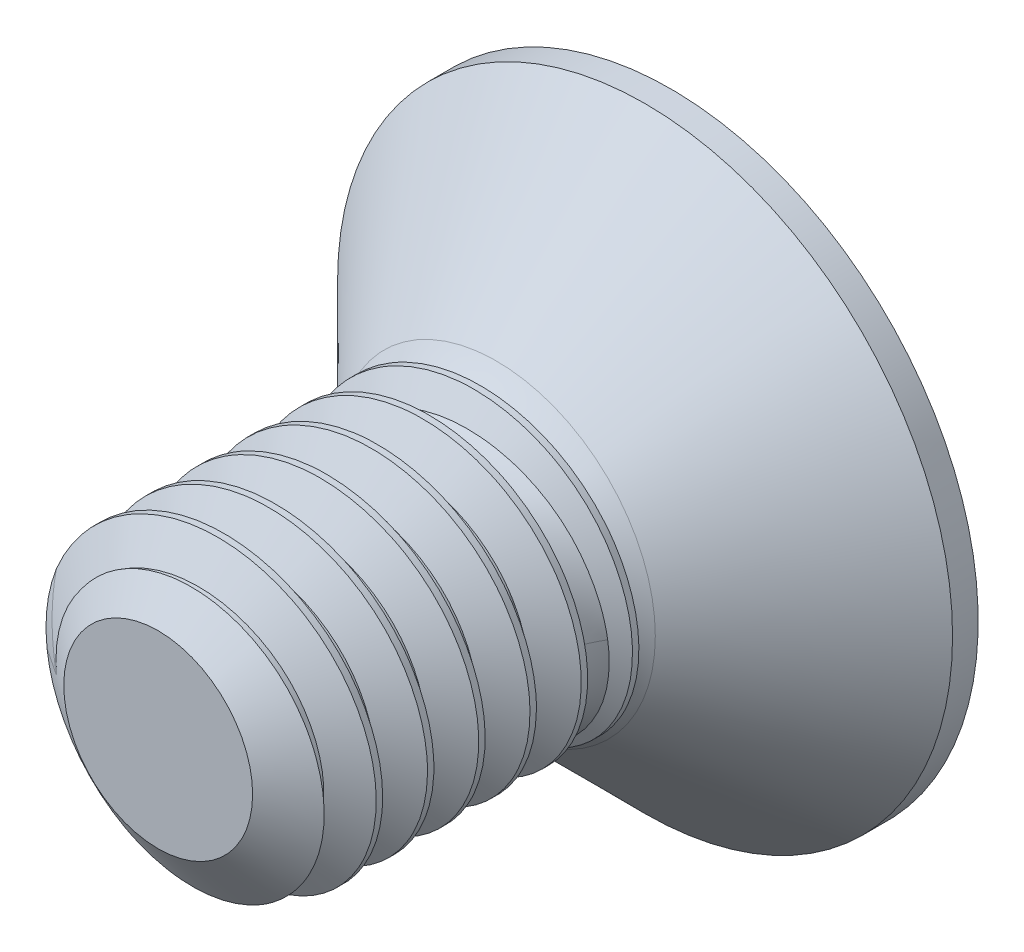
SolidWorks part; units mm, degrees
ref_plane "Front Plane" through (0, 0, 0) normal (0, 0, 1) x (1, 0, 0)
ref_plane "Top Plane" through (0, 0, 0) normal (0, 1, 0) x (1, 0, 0)
ref_plane "Right Plane" through (0, 0, 0) normal (1, 0, 0) x (0, 0, -1)
sketch "Sketch1" plane through (0, 0, 0) normal (0, 0, 1) x (1, 0, 0)
  circle A0 centre (0, 0) radius 1.5
  dimension "OD" = 3
extrude "Extrude1" add sketch "Sketch1" against normal blind 5
sketch "Sketch2" plane through (0, 0, 0) normal (0, 0, 1) x (1, 0, 0)
  circle A0 centre (0, 0) radius 1.5 construction
  circle A1 centre (0, 0) radius 1.5
curve "Helix/Spiral1" pitch 0.5 height 5.5 radius 1.5 centre (0, 0, 0) axis (0, 0, -1) start towards (0, 1, 0) parameters "pitch"=0.5
sketch "Sketch3" plane through (0, 0, 0) normal (1, 0, 0) x (0, 0, -1)
  line L0 (-0.4375, 1.5) -> (-0.25, 1.1752)
  line L1 (-0.25, 1.1752) -> (-0.1875, 1.1752)
  line L2 (-0.1875, 1.1752) -> (0, 1.5)
  line L3 (-0.4375, 1.5) -> (0, 1.5)
  line L4 (-0.2188, 1.5) -> (-0.2188, 1.1752) construction
  line L5 (-0.3438, 1.3376) -> (-0.0937, 1.3376) construction
  line L6 (0, 1.5) -> (0, -1.5) construction
  dimension "D1" = 0.0625
  dimension "D2" = 0.25
  dimension "D3" = 60
sweep "Cut-Sweep1" cut profiles "Sketch3" path "Helix/Spiral1"
sketch "Sketch4" plane through (0, 0, 0) normal (1, 0, 0) x (0, 0, -1)
  line L0 (0.4053, 1.5) -> (0, 0.9212)
  line L1 (0, 0.9212) -> (0, 1.5)
  line L2 (0.4053, 1.5) -> (0, 1.5)
  line L3 (-0.4375, 1.5) -> (0, 1.5) construction
  line L4 (0, 0) -> (7.0209, 0) construction
  dimension "D1" = 55
  dimension "D2" = 0.254
revolve "Cut-Revolve1" cut sketch "Sketch4" angle 360 about L4
sketch "Sketch5" plane through (0, 0, 0) normal (1, 0, 0) x (0, 0, -1)
  line L0 (5, -1.1822) -> (5, 1.0703) construction
  line L1 (5, 1.55) -> (18.1906, 1.55)
  line L2 (5, 1.55) -> (5, 0)
  line L3 (5, 0) -> (18, 0)
  line L4 (18, 1.2198) -> (18, 0)
  line L5 (18.1906, 1.55) -> (18, 1.2198)
  line L6 (0, 0) -> (9.9695, 0) construction
  point P3 (18, 1.55)
  point P10 (18, 1.55)
  dimension "D1" = 0.3302
  dimension "Thread min" = 18
  dimension "D2" = 0.05
  dimension "D3" = 30
revolve "partially thread" [suppressed] add sketch "Sketch5" angle 360 about L6
sketch "Sketch6" plane through (0, 0, -5) normal (0, 0, -1) x (-1, 0, 0)
  circle A0 centre (0, 0) radius 3
  dimension "head dia" = 6
extrude "Extrude2" add sketch "Sketch6" against normal blind 1.7
sketch "Sketch10" plane through (0, 0, 0) normal (1, 0, 0) x (0, 0, -1)
  line L0 (4.75, -3) -> (3.3, -1.55)
  line L1 (3.3, -1.55) -> (3.3, -3)
  line L2 (4.75, -3) -> (3.3, -3)
  line L3 (0, 0) -> (3.3, 0) construction
  line L4 (3.3, 3) -> (3.3, -3) construction
  line L5 (4.75, 3) -> (3.3, 3) construction
  line L6 (3.3, 1.55) -> (3.3, 3) construction
  line L7 (4.75, 3) -> (3.3, 1.55) construction
  line L8 (3.3, 3) -> (3.3, -3) construction
  line L9 (3.3, 1.55) -> (3.3, -1.55) construction
  dimension "D1" = 45
  dimension "D2" = 0.05
revolve "Cut-Revolve2" cut sketch "Sketch10" angle 360 about L3
sketch "Sketch11" plane through (0, 0, 0) normal (1, 0, 0) x (0, 0, -1)
  line L0 (-0.25, 1.1752) -> (-0.1875, 1.1752) construction
  line L1 (4.75, 3) -> (3.3, 1.55) construction
  line L2 (2.3953, 1.1752) -> (2.3953, 0)
  line L3 (2.3953, 0) -> (3.3, 0)
  line L4 (3.3, 1.55) -> (3.3, 0)
  line L5 (0, 0) -> (3.3, 0) construction
  arc A0 (3.3, 1.55) -> (2.3953, 1.1752) centre (2.3953, 2.4547) cw
revolve "Revolve1" add sketch "Sketch11" angle 360 about L3
sketch "Sketch7" plane through (0, 0, -5) normal (0, 0, 1) x (1, 0, 0)
  line L1 (0, 1.1547) -> (-1, 0.5774)
  line L2 (-1, 0.5774) -> (-1, -0.5774)
  line L3 (-1, -0.5774) -> (0, -1.1547)
  line L4 (0, -1.1547) -> (1, -0.5774)
  line L5 (1, -0.5774) -> (1, 0.5774)
  line L6 (1, 0.5774) -> (0, 1.1547)
  circle A0 centre (0, 0) radius 1 construction
  dimension "hex dia" = 2
extrude "Cut-Extrude1" cut sketch "Sketch7" along normal blind 1.5
sketch "Sketch8" plane through (0, 0, -5) normal (0, 0, 1) x (1, 0, 0)
  circle A0 centre (0, 0) radius 1.1547
extrude "Cut-Extrude2" cut sketch "Sketch8" along normal through all draft 45
sketch "Sketch9" plane through (0, 0, 0) normal (1, 0, 0) x (0, 0, -1)
  line L0 (0, 1.5) -> (0, -1.5) construction
  line L1 (2.75, 1.5) -> (2.75, -1.5) construction
  line L2 (3.3, 1.5) -> (3.3, -1.5) construction
  line L3 (3.3, -1.55) -> (3.3, -3) construction
  dimension "D1" = 2.75
equation "\"D3@Helix/Spiral1\" = \"screw length@Extrude1\"+\"pitch@Helix/Spiral1\""
equation "\"D1@Sketch3\" = \"pitch@Helix/Spiral1\"*.125"
equation "\"D2@Sketch3\" = \"pitch@Helix/Spiral1\"*.5"
equation "\"D1@Cut-Extrude1\" = \"hex dia@Sketch7\"*.75"
equation "\"D1@Sketch9\" = \"pitch@Helix/Spiral1\"*5.5"
equation "\"D2@Sketch10\" = \"D2@Sketch5\""
